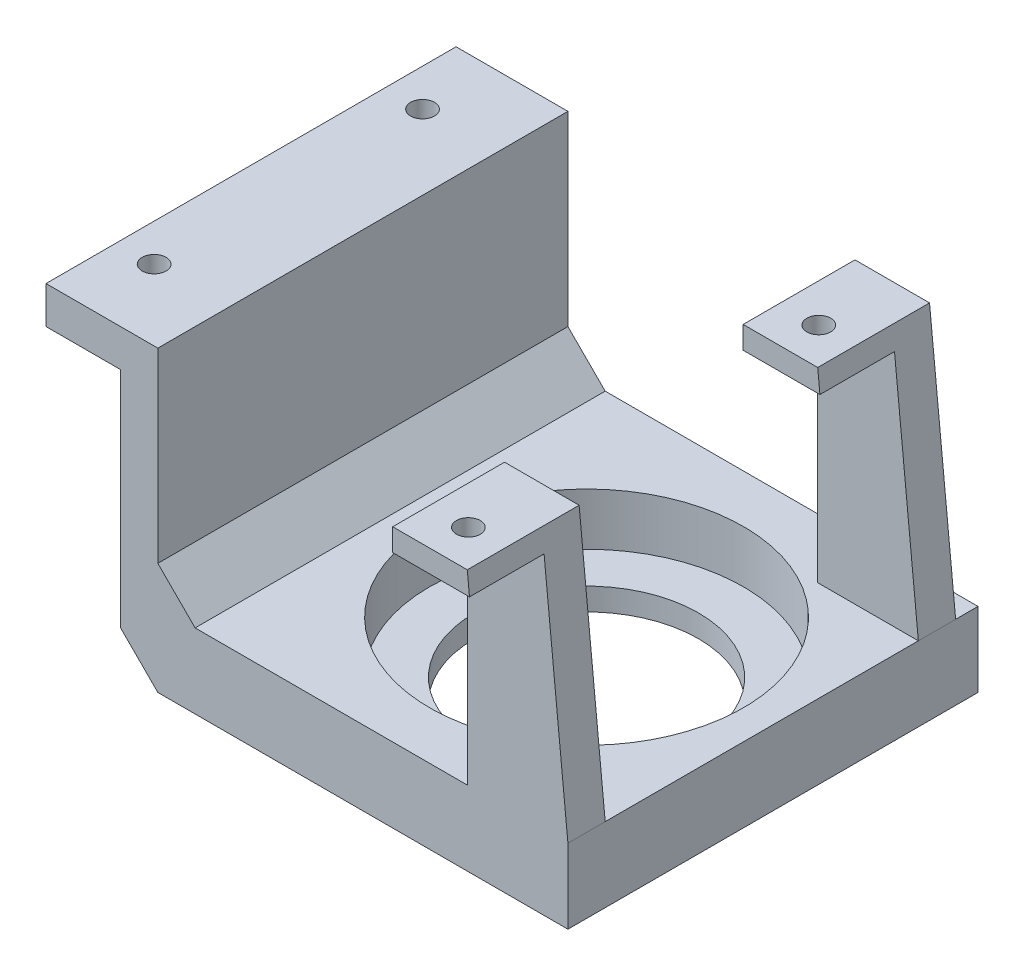
SolidWorks part; units mm, degrees
ref_plane "Alzado" through (0, 0, 0) normal (0, 0, 1) x (1, 0, 0)
ref_plane "Planta" through (0, 0, 0) normal (0, 1, 0) x (1, 0, 0)
ref_plane "Vista lateral" through (0, 0, 0) normal (1, 0, 0) x (0, 0, -1)
ref_plane "Plano1" through (0, 25, 0) normal (0, 1, 0) x (1, 0, 0)
sketch "Croquis4" plane through (0, 0, 0) normal (0, 0, 1) x (1, 0, 0)
  line L0 (-30, 5) -> (-30, 30)
  line L5 (-25, 5) -> (30, 5)
  line L6 (-30, 5) -> (-30, -5)
  line L7 (-30, -5) -> (30, -5)
  line L8 (30, 5) -> (30, -5)
  line L9 (-30, 5) -> (30, -5) construction
  line L10 (-30, -5) -> (30, 5) construction
  line L11 (-30, 30) -> (-40, 30)
  line L12 (-40, 30) -> (-40, 35)
  line L13 (-40, 35) -> (-25, 35)
  line L14 (-25, 35) -> (-25, 5)
  point P0 (0, 0)
  dimension "D1" = 10
  dimension "D2" = 60
  dimension "D3" = 5
  dimension "D4" = 5
  dimension "D5" = 10
  dimension "D6" = 10
  dimension "D7" = 30
extrude "Saliente-Extruir2" add sketch "Croquis4" along normal blind 55
sketch "Croquis6" plane through (0, 5, 0) normal (0, 1, 0) x (1, 0, 0)
  line L1 (30, -55) -> (30, 0) construction
  line L2 (30, -27.5) -> (-25, -27.5) construction
  line L3 (-25, -55) -> (-25, 0) construction
  circle A0 centre (5, -27.5) radius 21.05
  dimension "D1" = 42.1
  dimension "D3" = 25
extrude "Cortar-Extruir1" cut sketch "Croquis6" against normal blind 7
sketch "Croquis8" plane through (0, -2, 0) normal (0, 1, 0) x (1, 0, 0)
  circle A0 centre (5, -27.5) radius 15
  dimension "D1" = 30
extrude "Cortar-Extruir2" cut sketch "Croquis8" against normal through all both and the other way through all
sketch "Croquis9" plane through (0, 30, 0) normal (0, -1, 0) x (1, 0, 0)
  line L0 (-40, 27.5) -> (-30, 27.5) construction
  line L1 (-40, 55) -> (-40, 0) construction
  line L2 (-30, 55) -> (-30, 0) construction
  line L3 (-35, 27.5) -> (-35, 61.1151) construction
  circle A0 centre (-35, 45.5) radius 1.6
  circle A2 centre (-35, 9.5) radius 1.6
  dimension "D1" = 18
  dimension "D2" = 3.2
extrude "Cortar-Extruir3" cut sketch "Croquis9" against normal through all both and the other way through all
chamfer "Chaflán1" distance 5 angle 45 2 edges at (-25, 5, 27.5) (-30, -5, 27.5)
sketch "Croquis11" plane through (0, 5, 0) normal (0, 1, 0) x (1, 0, 0)
  line L1 (30, -55) -> (30, 0) construction
  line L4 (26.5, -55) -> (26.5, -40.1993) construction
  line L6 (30, -27.5) -> (-20, -27.5) construction
  line L7 (-20, 0) -> (-20, -55) construction
  line L12 (26.5, -55) -> (26.5, -50)
  line L13 (30, -55) -> (-20, -55) construction
  line L14 (26.5, -50) -> (16.5, -50)
  line L15 (16.5, -50) -> (16.5, -55)
  line L16 (16.5, -55) -> (26.5, -55)
  line L17 (26.5, -9) -> (26.5, -66) construction
  dimension "D1" = 10
  dimension "D2" = 5
extrude "Saliente-Extruir3" add sketch "Croquis11" along normal blind 35
sketch "Croquis13" plane through (0, 5, 0) normal (0, 1, 0) x (1, 0, 0)
  line L0 (26.5, -8) -> (26.5, -3)
  line L1 (26.5, -3) -> (16.5, -3)
  line L2 (16.5, -3) -> (16.5, -8)
  line L3 (16.5, -8) -> (26.5, -8)
  line L4 (26.5, -9) -> (26.5, 2.2982) construction
  line L5 (26.5, -9) -> (-5.5, -9) construction
  dimension "D1" = 5
  dimension "D2" = 10
  dimension "D3" = 1
extrude "Saliente-Extruir5" add sketch "Croquis13" along normal blind 35
sketch "Croquis16" plane through (0, 0, 55) normal (0, 0, 1) x (1, 0, 0)
  line L0 (30, 5) -> (26.5, 40)
  line L1 (26.5, 40) -> (26.5, 5)
  line L2 (26.5, 5) -> (30, 5)
extrude "Saliente-Extruir7" add sketch "Croquis16" against normal blind 5
sketch "Croquis17" plane through (0, 0, 8) normal (0, 0, 1) x (1, 0, 0)
  line L0 (30, 5) -> (26.5, 40)
  line L1 (26.5, 40) -> (26.5, 5)
  line L2 (26.5, 5) -> (30, 5)
extrude "Saliente-Extruir8" add sketch "Croquis17" against normal blind 5
sketch "Croquis19" plane through (0, 0, 55) normal (0, 0, 1) x (1, 0, 0)
  line L0 (16.5, 40) -> (16.5, 37)
  line L1 (16.5, 40) -> (16.5, 5) construction
  line L2 (16.5, 37) -> (26.8, 37)
  line L3 (30, 5) -> (26.5, 40) construction
  line L4 (26.8, 37) -> (26.5, 40)
  line L5 (26.5, 40) -> (16.5, 40)
  dimension "D1" = 3
extrude "Saliente-Extruir9" add sketch "Croquis19" along normal blind 10
sketch "Croquis20" plane through (0, 0, 8) normal (0, 0, 1) x (1, 0, 0)
  line L0 (16.5, 40) -> (16.5, 37)
  line L1 (16.5, 37) -> (26.8, 37)
  line L2 (26.8, 37) -> (26.5, 40)
  line L3 (26.5, 40) -> (16.5, 40)
extrude "Saliente-Extruir10" add sketch "Croquis20" along normal blind 10
sketch "Croquis15" plane through (0, 37, 0) normal (0, -1, 0) x (1, 0, 0)
  line L0 (21.65, 65) -> (21.65, 8) construction
  line L3 (26.8, 60) -> (21.65, 60) construction
  line L5 (26.8, 13) -> (16.5, 13) construction
  line L8 (16.5, 65) -> (26.8, 65) construction
  line L9 (26.8, 65) -> (26.8, 55) construction
  line L10 (26.8, 18) -> (26.8, 8) construction
  line L11 (16.5, 8) -> (26.8, 8) construction
  line L12 (16.5, 18) -> (16.5, 8) construction
  circle A0 centre (21.65, 60) radius 1.6
  circle A1 centre (21.65, 13) radius 1.6
  dimension "D1" = 3.2
extrude "Cortar-Extruir4" cut sketch "Croquis15" against normal through all
